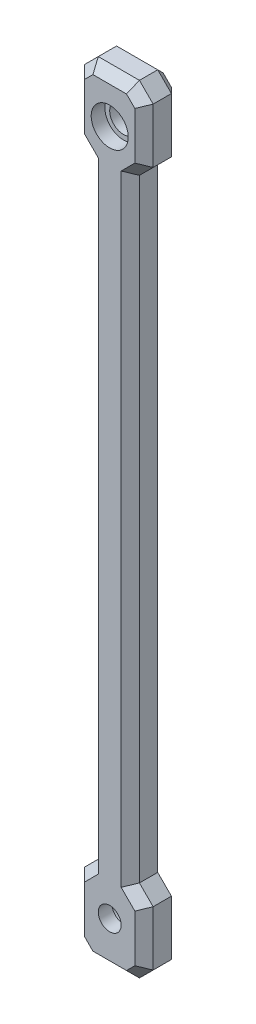
SolidWorks part; units mm, degrees
ref_plane "前视基准面" through (0, 0, 0) normal (0, 0, 1) x (1, 0, 0)
ref_plane "上视基准面" through (0, 0, 0) normal (0, 1, 0) x (1, 0, 0)
ref_plane "右视基准面" through (0, 0, 0) normal (1, 0, 0) x (0, 0, -1)
other "Configuration Table"
sketch "草图1" plane through (0, 0, 0) normal (0, 0, 1) x (1, 0, 0)
  line L0 (0, 96.7864) -> (0, -55.0987) construction
  line L1 (-7.5, 70) -> (-4.5, 70)
  line L2 (-7.5, -85) -> (7.5, -85)
  line L3 (-7.5, -85) -> (-7.5, -70)
  line L4 (-7.5, 85) -> (7.5, 85)
  line L5 (7.5, -85) -> (7.5, -70)
  line L6 (-7.5, -85) -> (7.5, 85) construction
  line L7 (-7.5, 85) -> (7.5, -85) construction
  line L8 (-4.5, 70) -> (-4.5, -70)
  line L9 (-4.5, -70) -> (-7.5, -70)
  line L10 (-7.5, 70) -> (-7.5, 85)
  line L11 (7.5, 70) -> (4.5, 70)
  line L12 (4.5, 70) -> (4.5, -70)
  line L13 (4.5, -70) -> (7.5, -70)
  line L14 (7.5, 70) -> (7.5, 85)
  circle A0 centre (0, -75) radius 2.5
  circle A1 centre (0, 75) radius 4.05
  point P1 (0, 0)
  dimension "D5" = 8.1
  dimension "D6" = 5
  dimension "D1" = 170
  dimension "D2" = 15
  dimension "D3" = 150
  dimension "D4" = 10
  dimension "D7" = 15
  dimension "D8" = 15
  dimension "D9" = 3
extrude "凸台-拉伸1" add sketch "草图1" along normal blind 8
chamfer "倒角2" distance 3 angle 45 8 edges at (-4.5, -70, 4) (4.5, -70, 4) (7.5, -85, 4) (-7.5, -85, 4) (-4.5, 70, 4) (4.5, 70, 4) (7.5, 85, 4) (-7.5, 85, 4)
ref_plane "基准面1" through (0, 0, 4) normal (0, 0, 1) x (1, 0, 0)
sketch "草图2" plane through (0, 0, 4) normal (0, 0, 1) x (1, 0, 0)
  circle A0 centre (0, 75) radius 4.05
  circle A1 centre (0, 75) radius 3
  dimension "D1" = 6
extrude "凸台-拉伸2" add sketch "草图2" along normal blind 1 and the other way blind 2
chamfer "倒角3" distance 2 angle 45 16 edges at (-6, -83.5, 8) (-7.5, -76, 8) (-6, -68.5, 8) (-4.5, 0, 8) (-6, 68.5, 8) (-7.5, 76, 8) (-6, 83.5, 8) (0, 85, 8) (6, 83.5, 8) (7.5, 76, 8) (6, 68.5, 8) (4.5, 0, 8) (6, -68.5, 8) (7.5, -76, 8) (6, -83.5, 8) (0, -85, 8)
chamfer "倒角4" distance 2 angle 45 16 edges at (6, -68.5, 0) (4.5, 0, 0) (6, 68.5, 0) (7.5, 76, 0) (6, 83.5, 0) (0, 85, 0) (-6, 83.5, 0) (-7.5, 76, 0) (-6, 68.5, 0) (-4.5, 0, 0) (-6, -68.5, 0) (-7.5, -76, 0) (-6, -83.5, 0) (0, -85, 0) (6, -83.5, 0) (7.5, -76, 0)
fillet "圆角1" radius 0.5 1 edges at (4.05, 75, 0)
fillet "圆角2" radius 0.5 1 edges at (2.5, -75, 0)
sketch "草图3" plane through (0, 0, 0) normal (0, 0, -1) x (-1, 0, 0)
  line L0 (-4.5, 85) -> (4.5, 85) construction
  line L1 (-9.3193, 62) -> (9.436, 62)
  line L2 (-9.3193, 62) -> (-9.3193, -86.1158)
  line L3 (-9.3193, -86.1158) -> (9.436, -86.1158)
  line L4 (9.436, 62) -> (9.436, -86.1158)
  dimension "D1" = 23
extrude "切除-拉伸1" cut sketch "草图3" against normal blind 2
chamfer "倒角5" distance 2 angle 45 1 edges at (0, 62, 2)
sketch "草图4" plane through (0, 0, 2) normal (0, 0, -1) x (-1, 0, 0)
  circle A0 centre (0, -75) radius 4.05
  dimension "D1" = 8.1
extrude "切除-拉伸2" cut sketch "草图4" against normal blind 3
fillet "圆角3" radius 0.5 1 edges at (-4.05, -75, 2)
